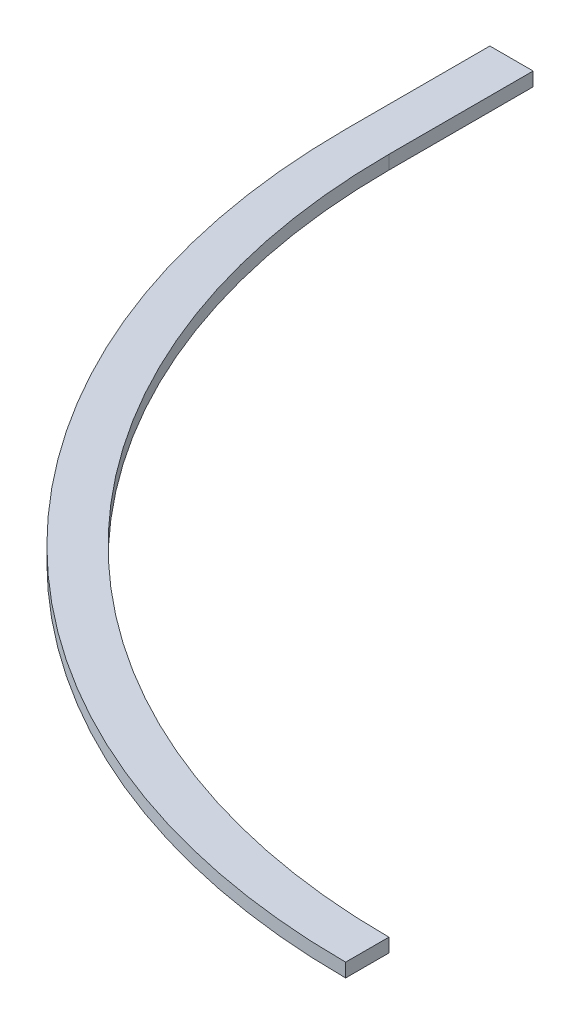
SolidWorks part; units mm, degrees
material "Pine"
ref_plane "Front Plane" through (0, 0, 0) normal (0, 0, 1) x (1, 0, 0)
ref_plane "Top Plane" through (0, 0, 0) normal (0, 1, 0) x (1, 0, 0)
ref_plane "Right Plane" through (0, 0, 0) normal (1, 0, 0) x (0, 0, -1)
sketch "Sketch2" plane through (0, 0, 0) normal (0, 1, 0) x (1, 0, 0)
  line L0 (0, 0) -> (-500, 0)
  line L1 (0, 0) -> (0, -500)
  circle A0 centre (0, 0) radius 500
  circle A1 centre (0, 0) radius 470
  dimension "D1" = 1000
  dimension "D2" = 30
extrude "Boss-Extrude1" add sketch "Sketch2" along normal blind 9.525 contours A1 L0 A0 L1 region at (-337.3402, 0, 337.3402)
sketch "Sketch3" plane through (0, 0, 0) normal (0, 0, -1) x (-1, 0, 0)
  line L8 (470, 0) -> (500, 0)
  line L9 (500, 0) -> (500, 9.525)
  line L10 (500, 9.525) -> (470, 9.525)
  line L11 (470, 9.525) -> (470, 0)
  line L12 (470, 0) -> (500, 0)
  line L13 (500, 0) -> (500, 9.525)
  line L14 (500, 9.525) -> (470, 9.525)
  line L15 (470, 9.525) -> (470, 0)
  dimension "D1" = 0
extrude "Boss-Extrude2" add sketch "Sketch3" along normal blind 100
